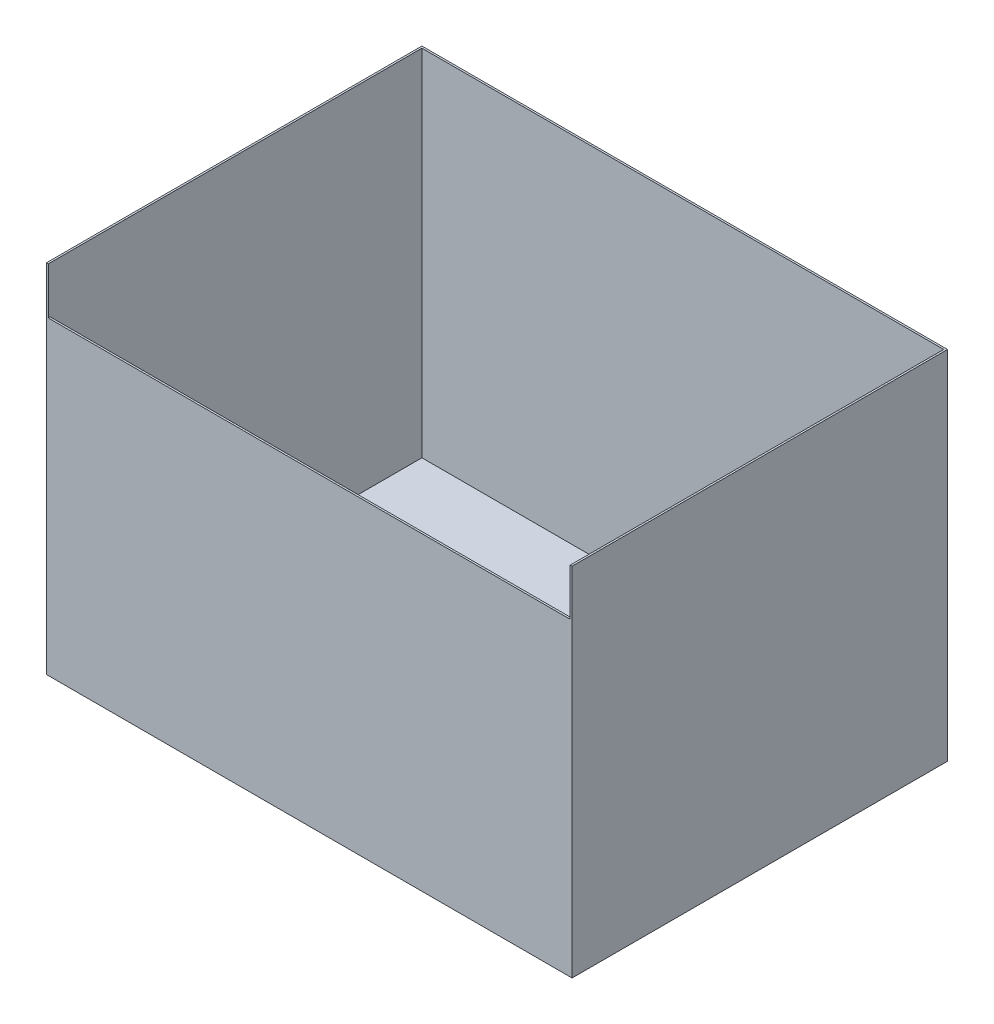
SolidWorks part; units mm, degrees
ref_plane "Front Plane" through (0, 0, 0) normal (0, 0, 1) x (1, 0, 0)
ref_plane "Top Plane" through (0, 0, 0) normal (0, 1, 0) x (1, 0, 0)
ref_plane "Right Plane" through (0, 0, 0) normal (1, 0, 0) x (0, 0, -1)
sketch "Sketch1" plane through (0, 0, 0) normal (0, 1, 0) x (1, 0, 0)
  line L0 (-355.6, 254) -> (355.6, -254) construction
  line L1 (-355.6, 254) -> (355.6, 254)
  line L2 (-355.6, 254) -> (-355.6, -254)
  line L3 (-355.6, -254) -> (355.6, -254)
  line L4 (355.6, 254) -> (355.6, -254)
  dimension "D1" = 711.2
  dimension "D2" = 508
extrude "Boss-Extrude1" add sketch "Sketch1" along normal mid plane 482.6
shell "Shell1" thickness 2.54 removed face at (0, 241.3, 0)
sketch "Sketch2" plane through (0, 0, 254) normal (0, 0, 1) x (1, 0, 0)
  line L0 (-355.6, 241.3) -> (-355.6, -241.3) construction
  line L1 (-353.06, 241.3) -> (353.06, 241.3)
  line L2 (-353.06, 241.3) -> (-353.06, 177.8)
  line L3 (-353.06, 177.8) -> (353.06, 177.8)
  line L4 (353.06, 241.3) -> (353.06, 177.8)
  line L5 (355.6, 241.3) -> (355.6, -241.3) construction
  line L6 (-355.6, 241.3) -> (355.6, 241.3) construction
  dimension "D1" = 63.5
  dimension "D2" = 2.54
  dimension "D3" = 2.54
extrude "Cut-Extrude1" cut sketch "Sketch2" against normal up to next
